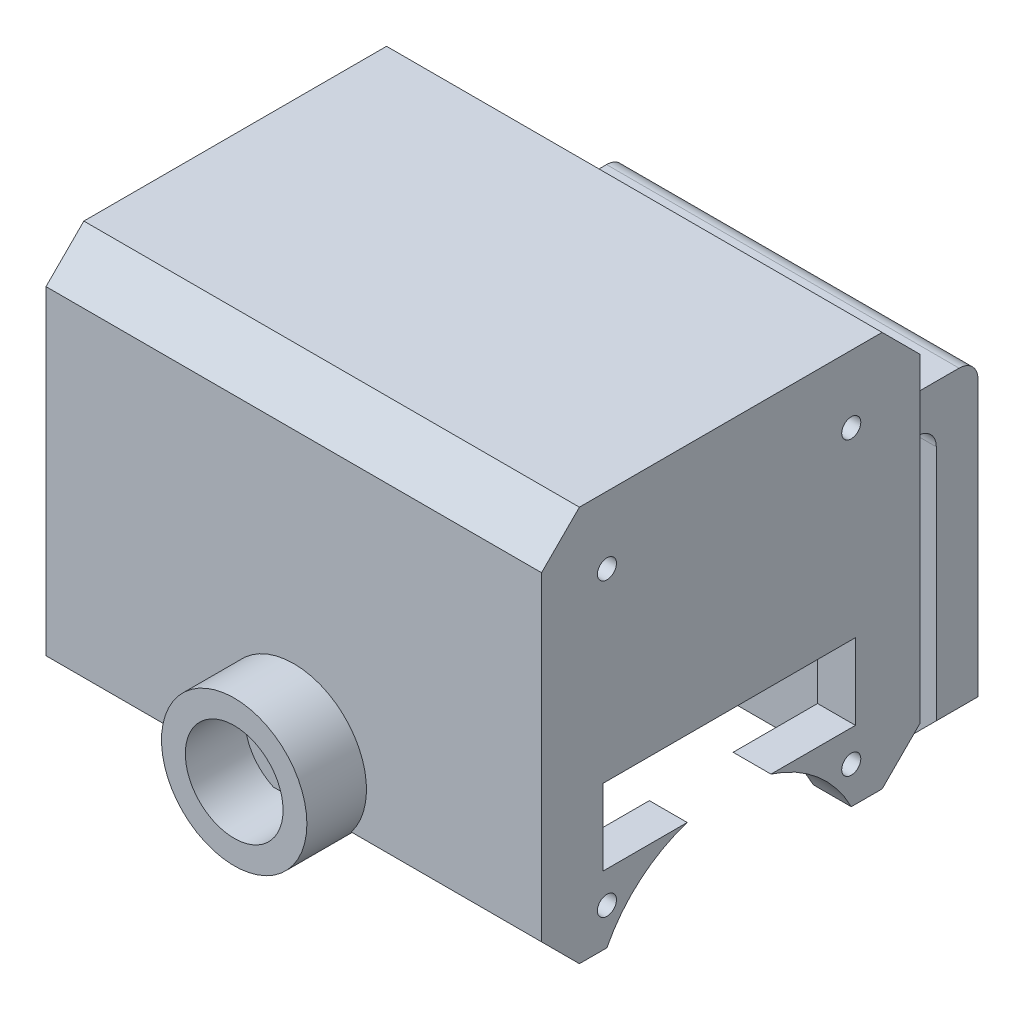
SolidWorks part; units mm, degrees
material "PLA"
ref_plane "Front Plane" through (0, 0, 0) normal (0, 0, 1) x (1, 0, 0)
ref_plane "Top Plane" through (0, 0, 0) normal (0, 1, 0) x (1, 0, 0)
ref_plane "Right Plane" through (0, 0, 0) normal (1, 0, 0) x (0, 0, -1)
sketch "Sketch1" plane through (0, 0, 0) normal (1, 0, 0) x (0, 0, -1)
  line L1 (0, 0) -> (25, 0)
  line L2 (0, 0) -> (0, 30)
  line L3 (0, 30) -> (25, 30)
  line L4 (25, 0) -> (25, 30)
  dimension "D1" = 30
  dimension "D2" = 25
extrude "Boss-Extrude1" add sketch "Sketch1" along normal blind 3.175
sketch "Sketch2" plane through (0, 0, 0) normal (-1, 0, 0) x (0, 0, 1)
  line L1 (-25, 30) -> (0, 30)
  line L2 (-25, 30) -> (-25, 33.175)
  line L3 (-25, 33.175) -> (0, 33.175)
  line L4 (0, 30) -> (0, 33.175)
  dimension "D1" = 3.175
extrude "Boss-Extrude2" add sketch "Sketch2" against normal blind 41.58
sketch "Sketch3" plane through (0, 30, 0) normal (0, -1, 0) x (1, 0, 0)
  line L0 (41.58, 0) -> (3.175, 0) construction
  line L1 (41.58, -25) -> (38.405, -25)
  line L2 (41.58, -25) -> (41.58, 0)
  line L3 (41.58, 0) -> (38.405, 0)
  line L4 (38.405, -25) -> (38.405, 0)
  dimension "D1" = 3.175
extrude "Boss-Extrude3" add sketch "Sketch3" along normal up to surface (30 mm away) up to face at (1.5875, 0, -12.5)
sketch "Sketch4" plane through (0, 0, 0) normal (-1, 0, 0) x (0, 0, 1)
  circle A0 centre (-12.36, -5.21) radius 11.5
  dimension "D1" = 23
extrude "Cut-Extrude1" cut sketch "Sketch4" against normal up to next
sketch "Sketch5" plane through (0, 0, 0) normal (-1, 0, 0) x (0, 0, 1)
  circle A0 centre (-22.61, 3.09) radius 0.8
  circle A1 centre (-22.61, 23.79) radius 0.8
  circle A2 centre (-2.11, 23.79) radius 0.8
  circle A3 centre (-2.11, 3.09) radius 0.8
extrude "Cut-Extrude2" cut sketch "Sketch5" against normal up to next
sketch "Sketch6" plane through (41.58, 0, 0) normal (1, 0, 0) x (0, 0, -1)
  line L1 (1.76, 5.74) -> (22.96, 5.74)
  line L2 (1.76, 5.74) -> (1.76, 12.115)
  line L3 (1.76, 12.115) -> (22.96, 12.115)
  line L4 (22.96, 5.74) -> (22.96, 12.115)
  circle A0 centre (2.11, 3.09) radius 0.8
  circle A1 centre (22.61, 3.09) radius 0.8
  circle A2 centre (22.61, 27.54) radius 0.7999
  circle A3 centre (2.11, 27.54) radius 0.8
extrude "Cut-Extrude3" cut sketch "Sketch6" against normal up to next
sketch "Sketch7" plane through (41.58, 0, 0) normal (1, 0, 0) x (0, 0, -1)
  circle A0 centre (12.36, -5.21) radius 11.5
  dimension "D1" = 23
extrude "Cut-Extrude4" cut sketch "Sketch7" against normal up to next
sketch "Sketch8" plane through (0, 0, 0) normal (0, 0, 1) x (1, 0, 0)
  line L8 (0, 33.175) -> (0, 0)
  line L9 (0, 0) -> (3.175, 0)
  line L10 (3.175, 0) -> (3.175, 30)
  line L11 (3.175, 30) -> (38.405, 30)
  line L12 (38.405, 30) -> (38.405, 0)
  line L13 (38.405, 0) -> (41.58, 0)
  line L14 (41.58, 0) -> (41.58, 33.175)
  line L15 (41.58, 33.175) -> (0, 33.175)
  line L16 (0, 33.175) -> (0, 0)
  line L17 (0, 0) -> (3.175, 0)
  line L18 (3.175, 0) -> (3.175, 30)
  line L19 (3.175, 30) -> (38.405, 30)
  line L20 (38.405, 30) -> (38.405, 0)
  line L21 (38.405, 0) -> (41.58, 0)
  line L22 (41.58, 0) -> (41.58, 33.175)
  line L23 (41.58, 33.175) -> (0, 33.175)
  dimension "D1" = 0
extrude "Boss-Extrude4" add sketch "Sketch8" along normal blind 0.2
sketch "Sketch9" plane through (0, 0, 0.2) normal (0, 0, 1) x (1, 0, 0)
  line L1 (0, 0) -> (41.58, 0)
  line L2 (0, 0) -> (0, 33.175)
  line L3 (0, 33.175) -> (41.58, 33.175)
  line L4 (41.58, 0) -> (41.58, 33.175)
extrude "Boss-Extrude5" add sketch "Sketch9" along normal blind 3.175
sketch "Sketch10" plane through (0, 0, -25) normal (0, 0, -1) x (-1, 0, 0)
  line L8 (0, 0) -> (0, 33.175)
  line L9 (0, 33.175) -> (-41.58, 33.175)
  line L10 (-41.58, 33.175) -> (-41.58, 0)
  line L11 (-41.58, 0) -> (-38.405, 0)
  line L12 (-38.405, 0) -> (-38.405, 30)
  line L13 (-38.405, 30) -> (-3.175, 30)
  line L14 (-3.175, 30) -> (-3.175, 0)
  line L15 (-3.175, 0) -> (0, 0)
  line L16 (0, 0) -> (0, 33.175)
  line L17 (0, 33.175) -> (-41.58, 33.175)
  line L18 (-41.58, 33.175) -> (-41.58, 0)
  line L19 (-41.58, 0) -> (-38.405, 0)
  line L20 (-38.405, 0) -> (-38.405, 30)
  line L21 (-38.405, 30) -> (-3.175, 30)
  line L22 (-3.175, 30) -> (-3.175, 0)
  line L23 (-3.175, 0) -> (0, 0)
  dimension "D1" = 0
extrude "Boss-Extrude6" add sketch "Sketch10" along normal blind 0.2
sketch "Sketch11" plane through (0, 0, -25.2) normal (0, 0, -1) x (-1, 0, 0)
  line L1 (-41.58, 0) -> (0, 0)
  line L2 (-41.58, 0) -> (-41.58, 33.175)
  line L3 (-41.58, 33.175) -> (0, 33.175)
  line L4 (0, 0) -> (0, 33.175)
extrude "Boss-Extrude7" add sketch "Sketch11" along normal blind 3.175
chamfer "Chamfer1" distance 3.175 angle 45 2 edges at (20.79, 33.175, 3.375) (20.79, 33.175, -28.375)
chamfer "Chamfer2" distance 3.175 angle 45 2 edges at (20.79, 0, 3.375) (20.79, 0, -28.375)
sketch "Sketch13" plane through (0, 0, -28.375) normal (0, 0, -1) x (-1, 0, 0)
  line L0 (0, 3.175) -> (0, 30) construction
  line L1 (-35.58, 18.175) -> (-6, 18.175)
  line L3 (-35.58, 21.35) -> (-6, 21.35)
  line L5 (-35.58, 21.35) -> (-35.58, 18.175)
  line L6 (-6, 21.35) -> (-6, 18.175)
  line L7 (-41.58, 30) -> (-41.58, 3.175) construction
  line L9 (-41.58, 3.175) -> (0, 3.175) construction
  dimension "D1" = 3.175
  dimension "D2" = 6
  dimension "D3" = 6
  dimension "D4" = 15
extrude "Boss-Extrude8" add sketch "Sketch13" along normal blind 7.695
sketch "Sketch14" plane through (0, 18.175, 0) normal (0, -1, 0) x (1, 0, 0)
  line L0 (35.58, -35.745) -> (35.58, -39.2524) construction
  line L1 (-0.7092, -39.245) -> (9.3147, -39.245) construction
  line L7 (6, -35.745) -> (6, -39.245)
  line L8 (6, -39.245) -> (35.58, -39.245)
  line L9 (35.58, -35.745) -> (35.58, -39.245)
  line L11 (35.58, -36.07) -> (6, -36.07) construction
  line L12 (6, -35.745) -> (35.58, -35.745)
  dimension "D1" = 3.5
  dimension "D2" = 3.175
  dimension "D3" = 3.5
extrude "Boss-Extrude9" add sketch "Sketch14" against normal up to surface and the other way blind 25 up to face at (20.79, 21.35, -32.2225)
chamfer "Chamfer3" distance 3.5 angle 45 2 edges at (35.58, -6.825, -37.495) (6, -6.825, -37.495)
fillet "Fillet1" radius 1.5875 2 edges at (20.79, 21.35, -39.245) (20.79, 18.175, -35.745)
fillet "Fillet2" radius 1.5875 1 edges at (20.79, 21.35, -28.375)
sketch "Sketch16" plane through (0, 0, -39.245) normal (0, 0, -1) x (-1, 0, 0)
  line L0 (-20.79, 19.7625) -> (-20.79, 6.9025) construction
  line L1 (-6, 19.7625) -> (-35.58, 19.7625) construction
  circle A0 centre (-20.79, 6.9025) radius 6.1
  dimension "D2" = 12.2
  dimension "D1" = 12.86
extrude "Cut-Extrude5" cut sketch "Sketch16" against normal up to next
sketch "Sketch20" plane through (0, 0, -35.745) normal (0, 0, 1) x (1, 0, 0)
  circle A0 centre (20.79, 6.9025) radius 6.1 construction
  circle A1 centre (20.79, 6.9025) radius 6.1 construction
  circle A2 centre (20.79, 6.9025) radius 4.1
  circle A3 centre (20.79, 6.9025) radius 8
  dimension "D1" = 8.2
  dimension "D2" = 16
extrude "Boss-Extrude11" add sketch "Sketch20" along normal blind 5
sketch "Sketch21" plane through (0, -6.825, 0) normal (0, -1, 0) x (1, 0, 0)
  line L0 (20.79, -30.745) -> (20.79, -35.745) construction
  line L1 (28.79, -30.745) -> (12.79, -30.745) construction
  line L2 (32.08, -35.745) -> (9.5, -35.745) construction
  circle A0 centre (20.79, -33.245) radius 1.025
  dimension "D1" = 2.05
extrude "Cut-Extrude6" cut sketch "Sketch21" against normal up to surface (25 mm away)
sketch "Sketch23" plane through (0, 0, 3.375) normal (0, 0, 1) x (1, 0, 0)
  circle A2 centre (20.79, 6.9025) radius 4.1
  circle A4 centre (20.79, 6.9025) radius 6.1
  dimension "D1" = 8.2
  dimension "D2" = 12.2
extrude "Boss-Extrude12" add sketch "Sketch23" against normal blind 1.2 and the other way blind 5
chamfer "Chamfer4" distance 1.5 angle 45 3 edges at (6, 20.5563, -28.375) (35.58, 20.5563, -28.375) (20.79, 18.175, -28.375)
